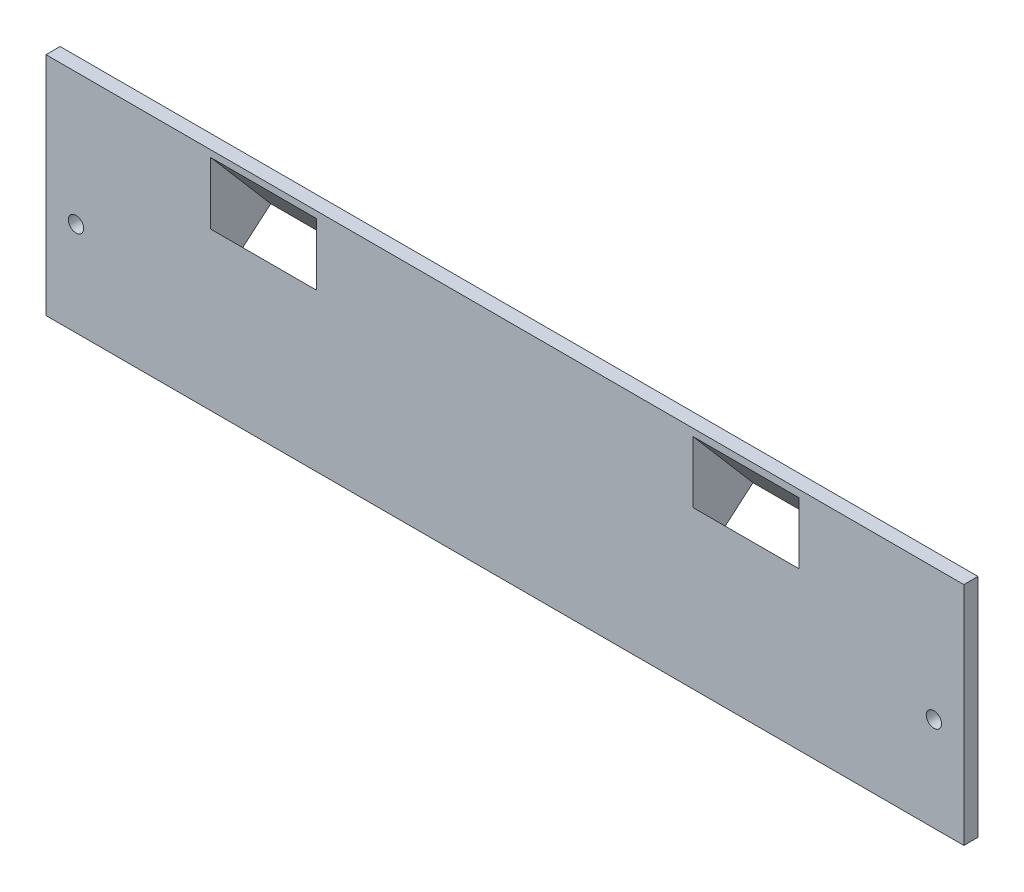
SolidWorks part; units mm, degrees
ref_plane "Alzado" through (0, 0, 0) normal (0, 0, 1) x (1, 0, 0)
ref_plane "Planta" through (0, 0, 0) normal (0, 1, 0) x (1, 0, 0)
ref_plane "Vista lateral" through (0, 0, 0) normal (1, 0, 0) x (0, 0, -1)
sketch "Croquis1" plane through (0, 0, 0) normal (0, 0, 1) x (1, 0, 0)
  line L0 (-97.5, 0) -> (97.5, 0)
  line L1 (97.5, 0) -> (97.5, 38)
  line L2 (97.5, 38) -> (-97.5, 38)
  line L3 (0, 0) -> (0, 28.0598) construction
  line L4 (-97.5, 0) -> (-97.5, 38)
  circle A2 centre (91.125, 15) radius 1.625
  circle A3 centre (-91.125, 15) radius 1.625
  point P13 (0, 38)
  point P14 (0, 0)
  dimension "D1" = 3.25
  dimension "D2" = 15
  dimension "D3" = 97.5
  dimension "D4" = 38
  dimension "D5" = 6.375
extrude "Saliente-Extruir1" add sketch "Croquis1" along normal blind 3
sketch "Croquis8" plane through (0, 0, 0) normal (0, -1, 0) x (1, 0, 0)
  line L1 (-97.5, 3) -> (97.5, 3)
  line L2 (-97.5, 3) -> (-97.5, 0)
  line L3 (-97.5, 0) -> (97.5, 0)
  line L4 (97.5, 3) -> (97.5, 0)
extrude "Saliente-Extruir5" add sketch "Croquis8" along normal blind 5
sketch "Croquis9" plane through (0, 38, 0) normal (0, 1, 0) x (1, 0, 0)
  line L1 (-97.5, 0) -> (97.5, 0)
  line L2 (-97.5, 0) -> (-97.5, -3)
  line L3 (-97.5, -3) -> (97.5, -3)
  line L4 (97.5, 0) -> (97.5, -3)
extrude "Saliente-Extruir6" add sketch "Croquis9" along normal blind 5
sketch "Croquis10" plane through (97.5, 0, 0) normal (1, 0, 0) x (0, 0, -1)
  line L0 (0, 39.4998) -> (11.1006, 26.5486)
  line L1 (1.23, 18.0885) -> (0, 17.0343)
  line L2 (0, 39.4998) -> (0, 17.0343)
  line L3 (0, -5) -> (0, 43) construction
  line L4 (11.1006, 26.5486) -> (1.23, 18.0885)
  line L6 (-3, 23.0238) -> (0, 19.5236) construction
  line L7 (-3, -5) -> (-3, 43) construction
  line L8 (-3, 23.0238) -> (5.5756, 30.374) construction
  dimension "D2" = 6.5
extrude "Saliente-Extruir7" add sketch "Croquis10" against normal blind 35 from offset 25 offset against normal yes
sketch "Croquis11" plane through (0, 9.8201, 8.4169) normal (0, -0.7593, -0.6508) x (1, 0, 0)
  line L0 (37.5, -11.0855) -> (37.5, -25.7055) construction
  line L3 (62.5, -16.2055) -> (40, -16.2055)
  line L6 (40, -16.2055) -> (40, -24.7055)
  line L7 (40, -24.7055) -> (62.5, -24.7055)
  line L8 (62.5, -24.7055) -> (62.5, -16.2055)
  line L10 (37.5, -25.7055) -> (72.5, -25.7055) construction
  dimension "D1" = 8.5
  dimension "D2" = 22.5
  dimension "D3" = 2.5
  dimension "D4" = 1
extrude "Cortar-Extruir4" cut sketch "Croquis11" against normal through all both and the other way through all
sketch "Croquis12" plane through (72.5, 0, 0) normal (1, 0, 0) x (0, 0, -1)
  line L0 (11.1006, 26.5486) -> (0, 17.0343)
  line L1 (0, 17.0343) -> (0, 23.6195)
  line L2 (0, -5) -> (0, 43) construction
  line L3 (0, 23.6195) -> (7.8467, 30.345)
  line L4 (11.1006, 26.5486) -> (0, 39.4998) construction
  line L5 (7.8467, 30.345) -> (11.1006, 26.5486)
  dimension "D1" = 5
extrude "Cortar-Extruir5" cut sketch "Croquis12" against normal up to next
sketch "Croquis13" plane through (0, 13.6165, 11.6707) normal (0, -0.7593, -0.6508) x (1, 0, 0)
  line L1 (62.5, -24.7055) -> (40, -24.7055) construction
  line L2 (72.5, -25.7055) -> (72.5, -15.371) construction
  circle A0 centre (66.25, -20.2055) radius 1
  dimension "D1" = 2
  dimension "D2" = 6.25
  dimension "D3" = 4.5
extrude "Cortar-Extruir6" cut sketch "Croquis13" against normal blind 5
sketch "Croquis14" plane through (-97.5, 0, 0) normal (-1, 0, 0) x (0, 0, 1)
  line L0 (0, 23.6195) -> (-7.8467, 30.345)
  line L1 (-7.8467, 30.345) -> (0, 39.4998)
  line L2 (0, 39.4998) -> (0, 23.6195)
extrude "Saliente-Extruir8" add sketch "Croquis14" against normal blind 35 from offset 25 offset against normal yes
sketch "Croquis16" plane through (0, 13.6165, 11.6707) normal (0, -0.7593, -0.6508) x (1, 0, 0)
  line L0 (0, 0) -> (0, -29.2293) construction
  line L5 (-40, -24.7778) -> (-62.5, -24.7778)
  line L6 (-62.5, -16.2055) -> (-62.5, -24.7778)
  line L7 (-40, -16.2055) -> (-40, -24.7778)
  line L8 (-40, -16.2055) -> (-62.5, -16.2055)
  line L15 (-37.5, -25.7055) -> (-37.5, -15.371) construction
  dimension "D1" = 2.5
extrude "Cortar-Extruir7" cut sketch "Croquis16" against normal through all both and the other way through all
sketch "Croquis17" plane through (0, 13.6165, 11.6707) normal (0, -0.7593, -0.6508) x (1, 0, 0)
  line L0 (0, 0) -> (0, -24) construction
  line L3 (-62.5, -16.2055) -> (-62.5, -24.7778) construction
  circle A1 centre (-66.25, -20.2055) radius 1
  dimension "D1" = 3.75
extrude "Cortar-Extruir8" cut sketch "Croquis17" against normal blind 5
sketch "Croquis18" plane through (0, 13.6165, 11.6707) normal (0, -0.7593, -0.6508) x (1, 0, 0)
  line L0 (-72.5, -25.7055) -> (-37.5, -25.7055)
  line L1 (-62.5, -16.2055) -> (-40, -16.2055)
  line L2 (-62.5, -16.2055) -> (-62.5, -24.7778)
  line L3 (-62.5, -24.7778) -> (-40, -24.7778)
  line L4 (-40, -16.2055) -> (-40, -24.7778)
  line L5 (40, -16.2055) -> (62.5, -16.2055)
  line L6 (40, -16.2055) -> (40, -24.7055)
  line L7 (40, -24.7055) -> (62.5, -24.7055)
  line L8 (62.5, -16.2055) -> (62.5, -24.7055)
  line L9 (-37.5, -25.7055) -> (-37.5, -13.7055)
  line L10 (-37.5, -13.7055) -> (-72.5, -13.7055)
  line L11 (-72.5, -13.7055) -> (-72.5, -25.7055)
  line L12 (37.5, -25.7055) -> (72.5, -25.7055)
  line L13 (72.5, -25.7055) -> (72.5, -13.7055)
  line L14 (72.5, -13.7055) -> (37.5, -13.7055)
  line L15 (37.5, -13.7055) -> (37.5, -25.7055)
  circle A0 centre (-66.25, -20.2055) radius 1
  circle A1 centre (66.25, -20.2055) radius 1
  dimension "D1" = 2.5
extrude "Saliente-Extruir9" add sketch "Croquis18" against normal up to surface (4.9736 mm away) from offset 4 up to face at (-55, 31.5597, 0)
